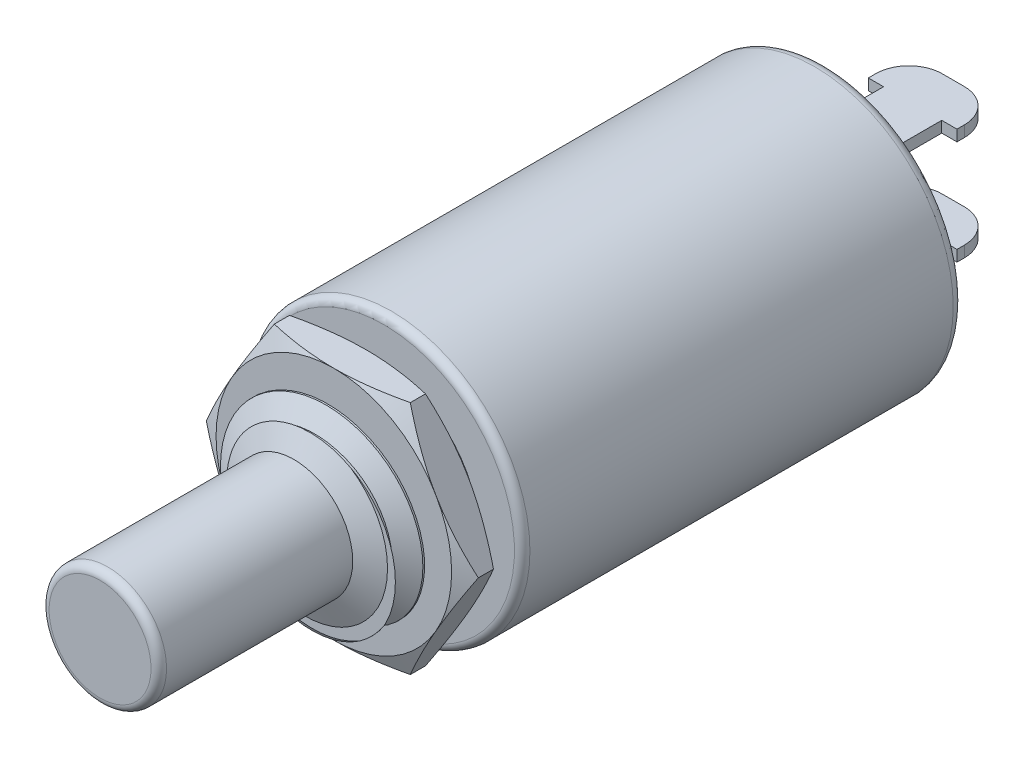
SolidWorks part; units mm, degrees
ref_plane "Front" through (0, 0, 0) normal (0, 0, 1) x (1, 0, 0)
ref_plane "Top" through (0, 0, 0) normal (0, 1, 0) x (1, 0, 0)
ref_plane "Right" through (0, 0, 0) normal (1, 0, 0) x (0, 0, -1)
sketch "Sketch1" plane through (0, 0, 0) normal (1, 0, 0) x (0, 0, -1)
  line L0 (0, 0) -> (19.558, 0) construction
  line L1 (0, 1.3462) -> (0, -1.3462) construction
  line L2 (4.445, 3.175) -> (4.445, -3.175) construction
  point P3 (4.445, 0)
  point P4 (7.62, 0)
  point P5 (16.637, 0)
  point P10 (6.2478, 0)
  point P11 (6.096, 0)
  dimension "D1" = 2.6924
  dimension "button" = 4.445
  dimension "D2" = 3.175
  dimension "D3" = 9.017
  dimension "D4" = 2.921
  dimension "D5" = 6.35
  dimension "D6" = 1.3722
  dimension "depth behind panel" = 13.462
sketch "Sketch2" plane through (0, 0, 0) normal (0, 0, 1) x (1, 0, 0)
  circle A0 centre (0, 0) radius 1.3462
extrude "Boss-Extrude1" add sketch "Sketch2" against normal up to vertex (4.445 mm away) up to point (0, 0, -4.445)
fillet "Fillet1" radius 0.1778 1 edges at (1.3462, 0, 0)
sketch "Sketch3" plane through (0, 0, -4.445) normal (0, 0, -1) x (-1, 0, 0)
  circle A0 centre (0, 0) radius 2.159
  dimension "D1" = 4.318
extrude "Boss-Extrude2" add sketch "Sketch3" along normal up to vertex (3.175 mm away) up to point (0, 0, -7.62)
sketch "Sketch4" plane through (0, 0, -4.445) normal (0, 0, 1) x (1, 0, 0)
  circle A0 centre (0, 0) radius 2.159 construction
  circle A1 centre (0, 0) radius 2.159
curve "Helix/Spiral1" pitch 0.635 height 3.556 radius 2.159 centre (0, 0, -4.445) axis (0, 0, -1) start towards (0, 1, 0)
sketch "Sketch5" plane through (0, 0, 0) normal (1, 0, 0) x (0, 0, -1)
  line L0 (3.81, 2.2277) -> (4.4847, 2.2277) construction
  line L1 (4.4847, 2.2277) -> (4.1473, 1.6434) construction
  line L2 (4.1473, 1.6434) -> (3.81, 2.2277) construction
  line L3 (3.8894, 2.0903) -> (4.4053, 2.0903) construction
  line L4 (4.1473, 2.2277) -> (4.1473, 2.159) construction
  line L5 (4.1473, 2.159) -> (4.1473, 2.0903) construction
  line L6 (4.1473, 2.159) -> (4.445, 2.159) construction
  line L7 (4.1077, 1.7122) -> (4.187, 1.7122) construction
  line L8 (4.1473, 1.7122) -> (4.1473, 1.6434) construction
  line L9 (3.81, 2.2277) -> (4.445, 2.159)
  line L10 (4.445, 2.159) -> (4.187, 1.7122)
  line L11 (4.187, 1.7122) -> (4.1077, 1.7122)
  line L12 (4.1077, 1.7122) -> (3.81, 2.2277)
  dimension "D1" = 0.635
  dimension "D2" = 0.0794
sweep "Cut-Sweep1" cut profiles "Sketch5" path "Helix/Spiral1" align with end faces yes
sketch "Sketch10" plane through (0, 0, -4.445) normal (0, 0, 1) x (1, 0, 0)
  circle A0 centre (0, 0) radius 1.3462 construction
  circle A1 centre (0, 0) radius 1.3462
extrude "Cut-Extrude4" cut sketch "Sketch10" against normal blind 0.254 draft 65 flip side to cut
ref_plane "Plane1" through (0, 0, -6.2478) normal (0, 0, 1) x (1, 0, 0)
sketch "Sketch7" plane through (0, 0, -6.2478) normal (0, 0, 1) x (1, 0, 0)
  line L1 (1.5588, -2.6999) -> (3.1176, 0)
  line L2 (3.1176, 0) -> (1.5588, 2.6999)
  line L3 (1.5588, 2.6999) -> (-1.5588, 2.6999)
  line L4 (-1.5588, 2.6999) -> (-3.1176, 0)
  line L5 (-3.1176, 0) -> (-1.5588, -2.6999)
  line L6 (-1.5588, -2.6999) -> (1.5588, -2.6999)
  circle A0 centre (0, 0) radius 2.6999 construction
  dimension "D1" = 5.3998
extrude "Boss-Extrude3" add sketch "Sketch7" against normal blind 0.254 and the other way blind 0.889 separate body
sketch "Sketch9" plane through (0, 0, -6.5018) normal (0, 0, -1) x (-1, 0, 0)
  line L0 (3.1176, 0) -> (1.5588, -2.6999) construction
  circle A0 centre (0, 0) radius 2.6999
extrude "Cut-Extrude3" cut sketch "Sketch9" against normal blind 0.254 draft 65 flip side to cut
sketch "Sketch11" plane through (0, 0, -6.5018) normal (0, 0, -1) x (-1, 0, 0)
  circle A0 centre (0, 0) radius 3.175
extrude "Boss-Extrude4" add sketch "Sketch11" along normal up to vertex (10.1352 mm away) separate body up to point (0, 0, -16.637)
fillet "Fillet2" radius 0.1778 1 edges at (-3.175, 0, -6.5018)
sketch "Sketch12" plane through (0, 0, -16.637) normal (0, 0, -1) x (-1, 0, 0)
  line L0 (0, 3.175) -> (0, -3.175) construction
  line L1 (-1.016, 1.3208) -> (1.016, 1.3208)
  line L2 (-1.016, 1.3208) -> (-1.016, 1.0668)
  line L3 (-1.016, 1.0668) -> (1.016, 1.0668)
  line L4 (1.016, 1.3208) -> (1.016, 1.0668)
  line L7 (0, 3.175) -> (0, 0) construction
  circle A0 centre (0, 0) radius 3.175 construction
  point P0 (0, 1.5875)
  point P12 (0, 1.5875)
  point P14 (0, 1.3208)
  dimension "D1" = 2.032
  dimension "D2" = 0.254
  dimension "D3" = 1.0668
extrude "Boss-Extrude5" add sketch "Sketch12" along normal up to vertex (2.921 mm away) separate body up to point (0, 0, -19.558)
sketch "Sketch13" plane through (0, 1.3208, 0) normal (0, 1, 0) x (1, 0, 0)
  line L0 (-1.016, 19.558) -> (-1.016, 16.637) construction
  line L1 (-1.3653, 18.6277) -> (-0.6667, 18.6277)
  line L2 (-1.3653, 18.6277) -> (-1.3653, 17.5673)
  line L3 (-1.3653, 17.5673) -> (-0.6667, 17.5673)
  line L4 (-0.6667, 18.6277) -> (-0.6667, 17.5673)
  line L5 (-1.3653, 18.6277) -> (-0.6667, 17.5673) construction
  line L6 (-1.3653, 17.5673) -> (-0.6667, 18.6277) construction
  line L7 (1.016, 19.558) -> (1.016, 16.637) construction
  line L8 (0.6667, 18.6277) -> (1.3653, 18.6277)
  line L9 (0.6667, 18.6277) -> (0.6667, 17.5673)
  line L10 (0.6667, 17.5673) -> (1.3653, 17.5673)
  line L11 (1.3653, 18.6277) -> (1.3653, 17.5673)
  line L12 (0.6667, 18.6277) -> (1.3653, 17.5673) construction
  line L13 (0.6667, 17.5673) -> (1.3653, 18.6277) construction
  point P0 (-1.016, 18.0975)
  point P7 (1.016, 18.0975)
  dimension "D1" = 0.6986
  dimension "D2" = 1.0605
extrude "Cut-Extrude5" cut sketch "Sketch13" against normal through all
fillet "Fillet3" radius 0.762 2 edges at (1.016, 1.1938, -19.558) (-1.016, 1.1938, -19.558)
mirror "Mirror1" about plane through (0, 0, 0) normal (0, 1, 0) of bodies 119
fillet "Fillet4" radius 0.254 1 edges at (-3.175, 0, -16.637)
ref_plane "Plane2" through (0, 0, -4.445) normal (0, 0, 1) x (1, 0, 0)
sketch "Sketch16" plane through (0, 0, -5.3588) normal (0, 0, 1) x (1, 0, 0)
  line L0 (1.5588, 2.6999) -> (-1.5588, 2.6999) construction
  circle A0 centre (0, 0) radius 2.6999
extrude "Cut-Extrude8" cut sketch "Sketch16" against normal blind 0.254 draft 65 flip side to cut
ref_plane "Plane3" through (0, 0, -6.096) normal (0, 0, 1) x (1, 0, 0)
sketch "Sketch17" plane through (0, 0, -6.096) normal (0, 0, 1) x (1, 0, 0)
  circle A0 centre (0, 0) radius 3.1176
  circle A1 centre (0, 0) radius 2.159
  circle A2 centre (0, 0) radius 2.159 construction
extrude "Cut-Extrude11" cut sketch "Sketch17" against normal up to surface (0.4058 mm away) up to face at (-2.9972, 0, -6.5018)
sketch "Sketch18" plane through (0, 0, -6.096) normal (0, 0, -1) x (-1, 0, 0)
  line L0 (-1.5588, 2.6999) -> (1.5588, 2.6999) construction
  circle A0 centre (0, 0) radius 2.6999
extrude "Cut-Extrude12" cut sketch "Sketch18" against normal blind 0.254 draft 65 flip side to cut
equation "\"D2@Sketch5\"=\"D1@Sketch5\"/8"
equation "\"D1@Sketch5\"=\"D4@Helix/Spiral1\""
